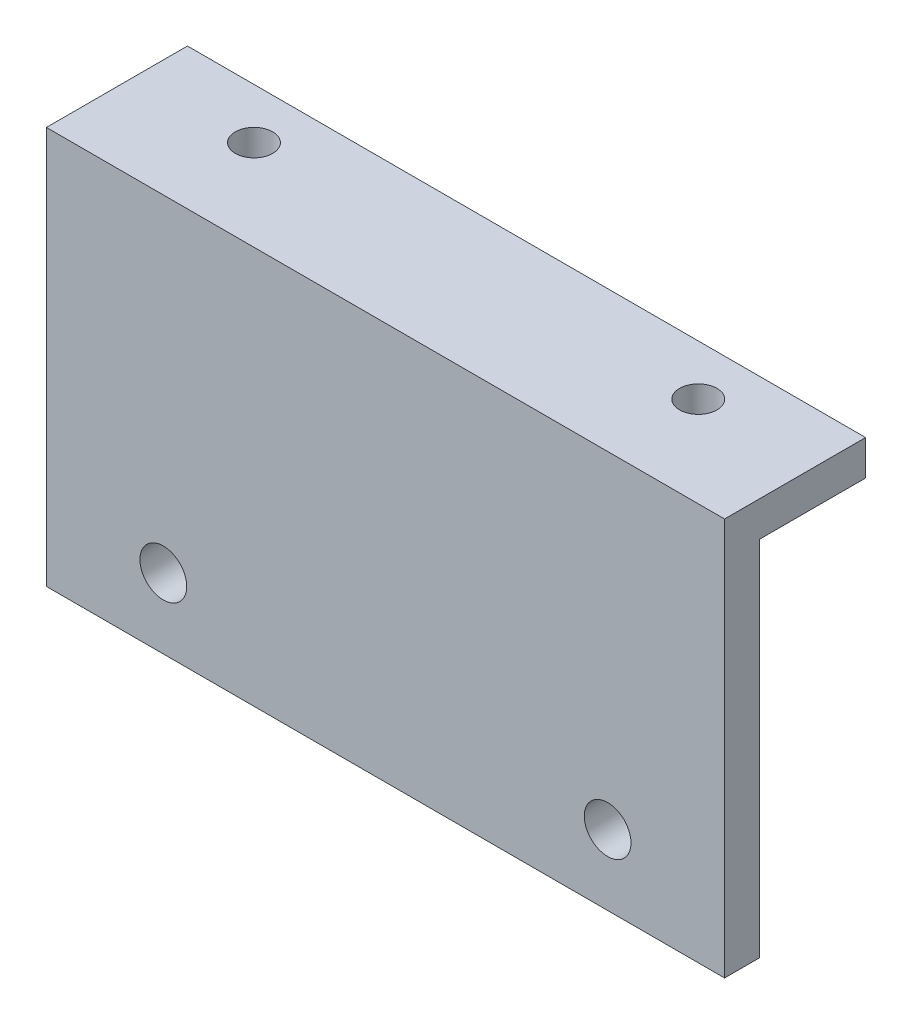
SolidWorks part; units mm, degrees
ref_plane "Front Plane" through (0, 0, 0) normal (0, 0, 1) x (1, 0, 0)
ref_plane "Top Plane" through (0, 0, 0) normal (0, 1, 0) x (1, 0, 0)
ref_plane "Right Plane" through (0, 0, 0) normal (1, 0, 0) x (0, 0, -1)
sketch "Sketch1" plane through (0, 0, 0) normal (0, 0, 1) x (1, 0, 0)
  line L0 (-29, -11) -> (29, -11) construction
  line L1 (-29, 17) -> (29, 17)
  line L2 (-29, 17) -> (-29, -17)
  line L3 (-29, -17) -> (29, -17)
  line L4 (29, 17) -> (29, -17)
  line L5 (-29, 17) -> (29, -17) construction
  line L6 (-29, -17) -> (29, 17) construction
  line L7 (0, 17) -> (0, -17) construction
  circle A0 centre (-19, -11) radius 2
  circle A1 centre (19, -11) radius 2
  point P0 (0, 0)
  dimension "D3" = 4
  dimension "D1" = 58
  dimension "D2" = 38
  dimension "D4" = 28
  dimension "D5" = 34
extrude "Boss-Extrude1" add sketch "Sketch1" along normal blind 3
sketch "Sketch2" plane through (0, 17, 0) normal (0, 1, 0) x (1, 0, 0)
  line L0 (-29, -3) -> (29, -3)
  line L1 (29, -3) -> (29, 9.0627)
  line L2 (29, 9.0627) -> (-29, 9.0627)
  line L3 (-29, 9.0627) -> (-29, -3)
  line L4 (-29, 4.7507) -> (29, 4.7507) construction
  line L5 (0, 9.0627) -> (0, -3) construction
  circle A0 centre (-19, 4.7507) radius 1.6
  circle A1 centre (19, 4.7507) radius 1.6
  dimension "D1" = 3.2
  dimension "D2" = 38
extrude "Boss-Extrude2" add sketch "Sketch2" against normal blind 3
